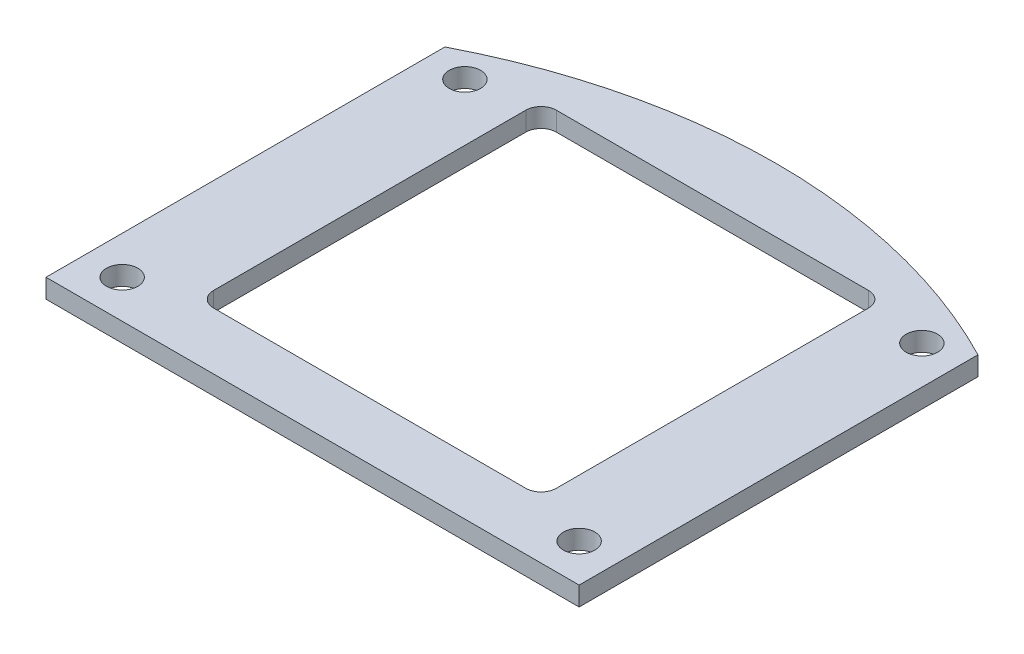
SolidWorks part; units mm, degrees
ref_plane "Front Plane" through (0, 0, 0) normal (0, 0, 1) x (1, 0, 0)
ref_plane "Top Plane" through (0, 0, 0) normal (0, 1, 0) x (1, 0, 0)
ref_plane "Right Plane" through (0, 0, 0) normal (1, 0, 0) x (0, 0, -1)
sketch "Sketch1" plane through (0, 0, 0) normal (0, 1, 0) x (1, 0, 0)
  line L1 (-28, -24) -> (28, -24)
  line L2 (-28, -24) -> (-28, 17.8957)
  line L4 (28, -24) -> (28, 17.8957)
  line L7 (-18, -18) -> (18, -18)
  line L8 (-18, -18) -> (-18, 18)
  line L9 (-18, 18) -> (18, 18)
  line L10 (18, -18) -> (18, 18)
  circle A0 centre (-24, 16) radius 1.65
  circle A1 centre (-24, -20) radius 1.65
  circle A2 centre (24, 16) radius 1.65
  circle A3 centre (24, -20) radius 1.65
  arc A4 (-17.9676, 18) -> (-18, 17.9893) centre (0, -36.3) ccw
  arc A10 (28, 17.8957) -> (-28, 17.8957) centre (0, -36.3) ccw
  arc A11 (28.3, 18.0781) -> (-28.3, 18.0781) centre (0, -36.3) ccw construction
  point P0 (0, 0)
  point P5 (0, 0)
  point P20 (0, 0)
  point P23 (0, 0)
  dimension "D5" = 16
  dimension "D6" = 4
  dimension "D7" = 4
  dimension "D8" = 16
  dimension "D9" = 3.3
  dimension "D10" = 3.3
  dimension "D11" = 4
  dimension "D12" = 4
  dimension "D13" = 4
  dimension "D15" = 3.3
  dimension "D16" = 3.3
  dimension "D17" = 4
  dimension "D22" = 0.3
  dimension "D3" = 36
  dimension "D4" = 36
  dimension "D14" = 56
  dimension "D18" = 18
  dimension "D19" = 18
  dimension "D20" = 24
  dimension "D21" = 28
extrude "Boss-Extrude1" add sketch "Sketch1" along normal blind 2 contours L4 L2 L1 L10 L7 L8 L9 A0 A1 A2 A3 region at (-27.2579, 0, 3.0521)
fillet "Fillet1" radius 1.6 4 edges at (-18, 1, 18) (18, 1, 18) (18, 1, -18) (-18, 1, -18)
